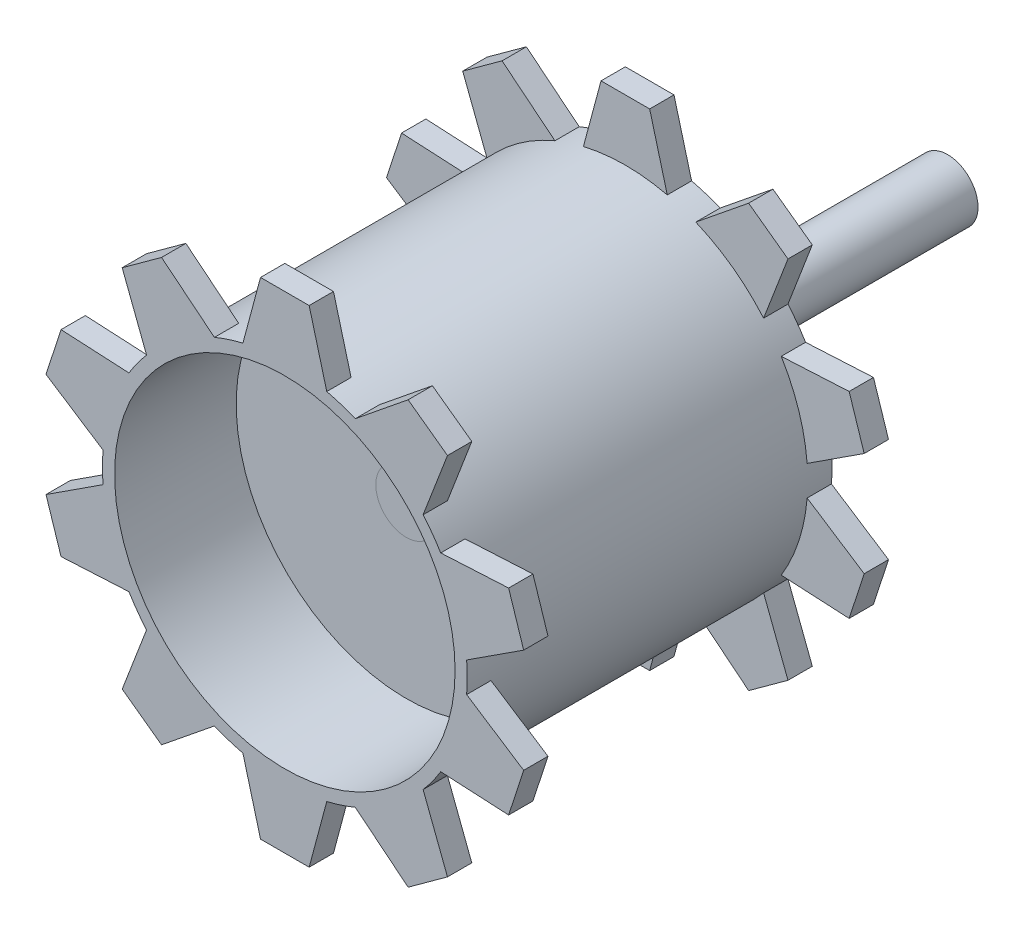
SolidWorks part; units mm, degrees
ref_plane "Front Plane" through (0, 0, 0) normal (0, 0, 1) x (1, 0, 0)
ref_plane "Top Plane" through (0, 0, 0) normal (0, 1, 0) x (1, 0, 0)
ref_plane "Right Plane" through (0, 0, 0) normal (1, 0, 0) x (0, 0, -1)
sketch "Sketch2" plane through (0, 0, 0) normal (0, 0, 1) x (1, 0, 0)
  circle A0 centre (0, 0) radius 70
  dimension "D1" = 140
extrude "Boss-Extrude1" add sketch "Sketch2" along normal blind 25 and the other way blind 25
sketch "Sketch3" plane through (0, 0, 25) normal (0, 0, 1) x (1, 0, 0)
  circle A0 centre (0, 0) radius 70
  circle A1 centre (0, 0) radius 75
  dimension "D1" = 150
  dimension "D2" = 140
extrude "Boss-Extrude2" add sketch "Sketch3" along normal blind 50 and the other way blind 100
sketch "Sketch4" plane through (0, 0, 75) normal (0, 0, 1) x (1, 0, 0)
  line L0 (0, 75) -> (0, 100) construction
  line L1 (-10, 100) -> (10, 100)
  line L2 (10, 100) -> (17.2367, 72.9925)
  line L3 (-10, 100) -> (-17.2367, 72.9925)
  circle A0 centre (0, 0) radius 75 construction
  arc A2 (17.2367, 72.9925) -> (-17.2367, 72.9925) centre (0, 0) ccw
  dimension "D1" = 25
  dimension "D2" = 10
  dimension "D3" = 105
extrude "Boss-Extrude3" add sketch "Sketch4" against normal blind 10
pattern_circular "CirPattern1" count 10 over 360 about axis through (0, 0, 75) along (0, 0, 1) of "Boss-Extrude3"
ref_plane "Plane1" through (0, 0, 0) normal (0, 0, 1) x (1, 0, 0)
mirror "Mirror1" about plane through (0, 0, 0) normal (0, 0, 1) of "CirPattern1"
sketch "Sketch5" plane through (0, 0, 25) normal (0, 0, 1) x (1, 0, 0)
  circle A0 centre (0, 0) radius 12.5
  dimension "D1" = 25
extrude "Boss-Extrude4" add sketch "Sketch5" against normal blind 222.4937 and the other way blind 0.1 separate body
